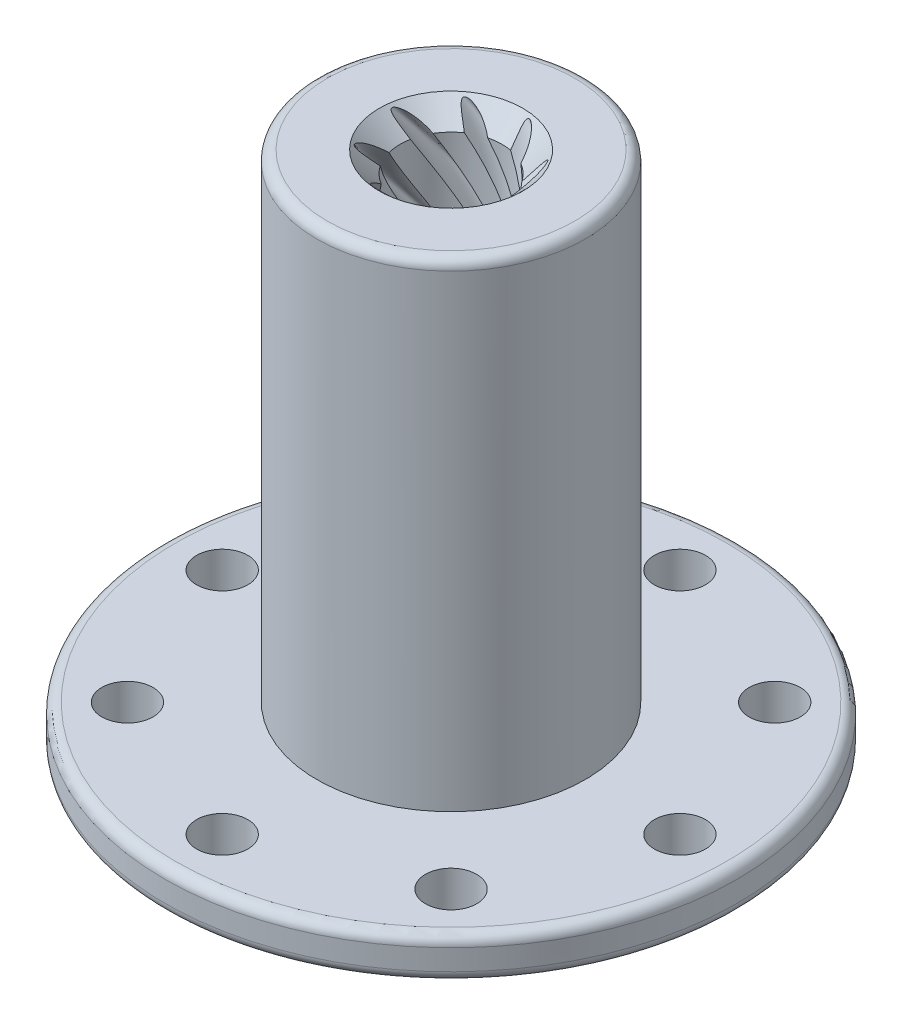
SolidWorks part; units mm, degrees
material "AISI 1035 Acier (SS)"
ref_plane "Plan de face" through (0, 0, 0) normal (0, 0, 1) x (1, 0, 0)
ref_plane "Plan de dessus" through (0, 0, 0) normal (0, 1, 0) x (1, 0, 0)
ref_plane "Plan de droite" through (0, 0, 0) normal (1, 0, 0) x (0, 0, -1)
sketch "Esquisse1" plane through (0, 0, 0) normal (0, 0, 1) x (1, 0, 0)
  line L0 (6.45, 25) -> (6.45, 2)
  line L1 (6.45, 2) -> (13.75, 2)
  line L2 (13.75, 2) -> (13.75, 0)
  line L11 (13.75, 0) -> (2.45, 0)
  line L12 (0, 0) -> (0, 15) construction
  line L13 (2.45, 0) -> (2.45, 24)
  line L14 (2.45, 24) -> (3.45, 25)
  line L15 (3.45, 25) -> (6.45, 25)
  line L16 (3.45, 25) -> (-0.2835, 25) construction
  dimension "D1" = 6.45
  dimension "D2" = 2
  dimension "D3" = 25
  dimension "D4" = 1
  dimension "D5" = 13.75
  dimension "D6" = 45
  dimension "D7" = 3
revolve "Révolution2" add sketch "Esquisse1" angle 360 about L12
fillet "Congé1" radius 0.5 3 edges at (0, 0, -13.75) (0, 2, -13.75) (0, 25, -6.45)
sketch "Esquisse8" plane through (0, 2, 0) normal (0, 1, 0) x (1, 0, 0)
  circle A0 centre (11, 0) radius 1.23
  point P2 (0, 0)
  point P12 (0, 0)
  dimension "D1" = 1.23
  dimension "D2" = 11
extrude "Enlèv. mat.-Extru.2" cut sketch "Esquisse8" against normal through all
pattern_circular "Répétition circulaire2" count 8 over 360 about axis through (0, 0, 0) along (0, -1, 0) of "Enlèv. mat.-Extru.2" reverse direction yes
sketch "Esquisse9" plane through (0, 0, 0) normal (0, -1, 0) x (1, 0, 0)
  circle A0 centre (0, 0) radius 3.325
  dimension "D1" = 6.65
curve "Hélice/Spirale1" pitch 25.4 height 25 radius 3.325 centre (0, 0, 0) axis (0, 1, 0) start towards (0, 0, -1)
sketch "Esquisse11" plane through (0, 0, 0) normal (0, 0, 1) x (1, 0, 0)
  line L0 (2.3245, 19.852) -> (2.3245, 18.352)
  line L1 (0, 0) -> (0, 23.2557) construction
  line L2 (-2.45, 0) -> (2.45, 0) construction
  line L3 (0, 19.102) -> (4.8111, 19.102) construction
  spline S4 degree 2 poles (2.3245, 18.352) (4.3245, 19.102) (2.3245, 19.852) knots 0 0 0 1 1 1
  spline S5 degree 3 poles (0, 0) (-0.4556, 0.554) (-1.3712, 1.6674) (-2.5114, 3.3331) (-3.2316, 5.0001) (-3.41, 6.6667) (-3.0171, 8.3333) (-2.1185, 10) (-0.8649, 11.6667) (0.5337, 13.3333) (1.8428, 15) (2.8431, 16.6667) (3.3669, 18.3333) (3.3266, 19.9999) (2.7285, 21.6669) (1.6741, 23.3326) (0.7819, 24.446) (0.3285, 25) knots 0 0 0 0 0.066667 0.133333 0.2 0.266667 0.333333 0.4 0.466667 0.533333 0.6 0.666667 0.733333 0.8 0.866667 0.933333 1 1 1 1 construction
  dimension "D1" = 0.75
  dimension "D2" = 0.75
  dimension "D4" = 1
sweep "Enlèvement de matière-Balayage1" cut profiles "Esquisse11" path "Hélice/Spirale1"
pattern_circular "Répétition circulaire1" count 8 over 360 about axis through (0, 0, 0) along (0, -1, 0) of "Enlèvement de matière-Balayage1"
